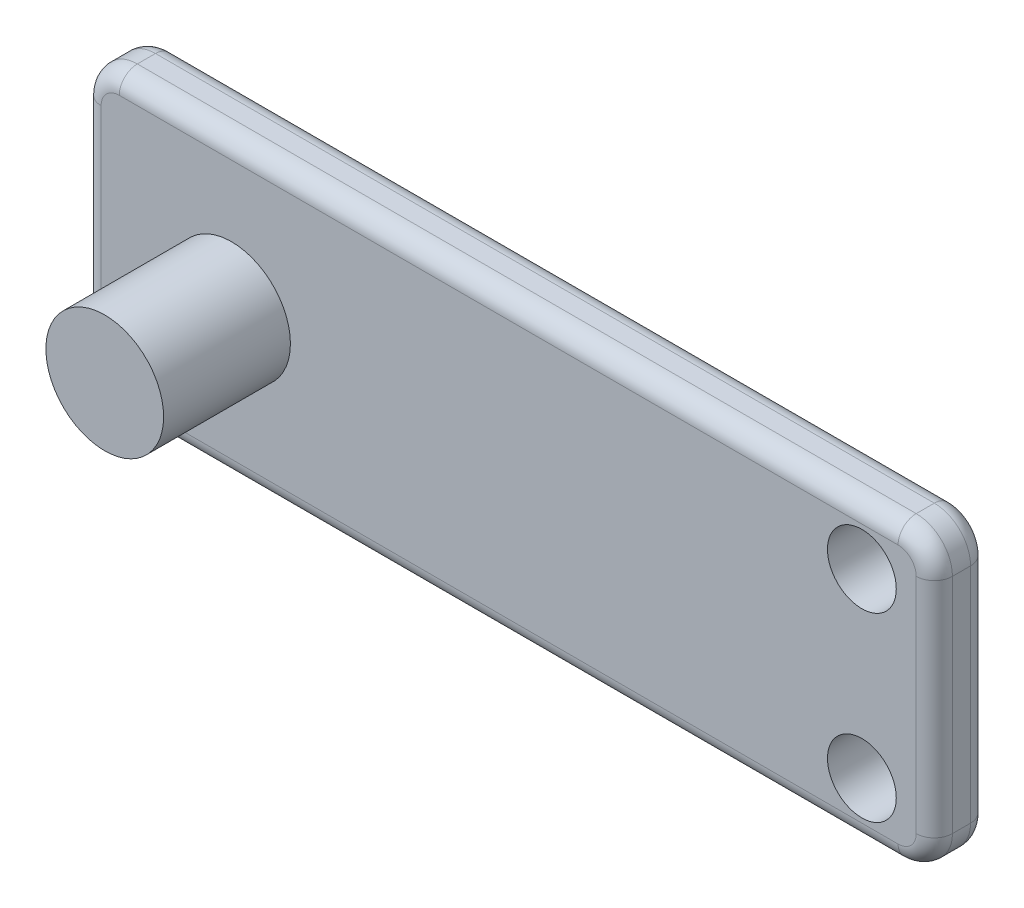
SolidWorks part; units mm, degrees
ref_plane "Front Plane" through (0, 0, 0) normal (0, 0, 1) x (1, 0, 0)
ref_plane "Top Plane" through (0, 0, 0) normal (0, 1, 0) x (1, 0, 0)
ref_plane "Right Plane" through (0, 0, 0) normal (1, 0, 0) x (0, 0, -1)
sketch "Sketch1" plane through (0, 0, 0) normal (0, 0, 1) x (1, 0, 0)
  line L0 (0, 0) -> (54.8775, 0) construction
  line L1 (-23.5, 8.15) -> (23.5, 8.15)
  line L2 (-23.5, 8.15) -> (-23.5, -8.15)
  line L3 (-23.5, -8.15) -> (23.5, -8.15)
  line L4 (23.5, 8.15) -> (23.5, -8.15)
  line L5 (-23.5, 8.15) -> (23.5, -8.15) construction
  line L6 (-23.5, -8.15) -> (23.5, 8.15) construction
  line L7 (19.5, 5) -> (19.5, -5) construction
  circle A0 centre (19.5, 5) radius 1.9
  circle A1 centre (19.5, -5) radius 1.9
  point P0 (0, 0)
  dimension "D3" = 3.8
  dimension "D4" = 3.8
  dimension "D1" = 16.3
  dimension "D2" = 47
  dimension "D5" = 10
  dimension "D6" = 5
  dimension "D7" = 4
extrude "Boss-Extrude1" add sketch "Sketch1" along normal blind 3
sketch "Sketch2" plane through (0, 0, 0) normal (0, 0, 1) x (1, 0, 0)
  circle A0 centre (-15.3, 0) radius 3.25
  dimension "D1" = 6.5
extrude "Boss-Extrude2" add sketch "Sketch2" along normal blind 10
fillet "Fillet1" radius 1 8 edges at (23.5, 0, 0) (0, -8.15, 0) (-23.5, 0, 0) (0, 8.15, 0) (0, 8.15, 3) (-23.5, 0, 3) (0, -8.15, 3) (23.5, 0, 3)
fillet "Fillet2" radius 2 12 edges at (-23.2071, -7.8571, 0.2929) (-23.2071, -7.8571, 2.7071) (-23.2071, 7.8571, 0.2929) (-23.2071, 7.8571, 2.7071) (23.2071, -7.8571, 0.2929) (23.2071, -7.8571, 2.7071) (23.2071, 7.8571, 0.2929) (23.2071, 7.8571, 2.7071) (23.5, 8.15, 1.5) (23.5, -8.15, 1.5) (-23.5, 8.15, 1.5) (-23.5, -8.15, 1.5)
